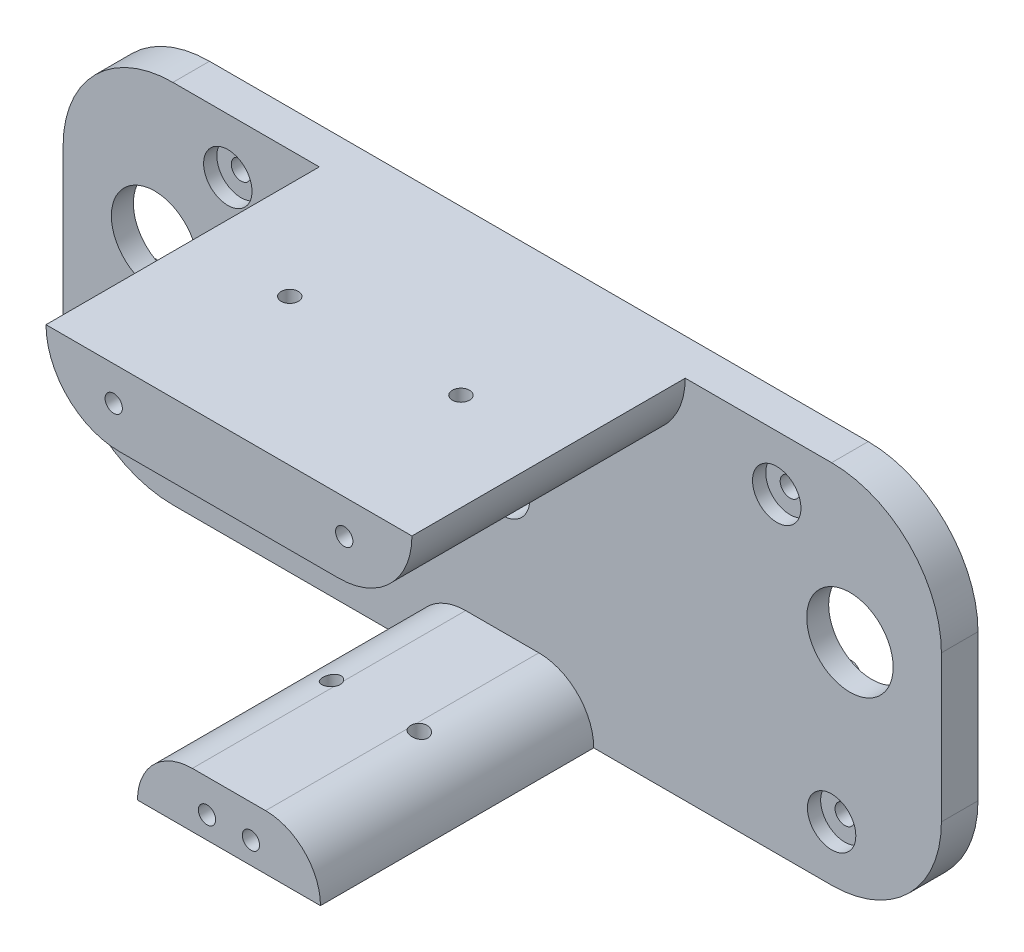
SolidWorks part; units mm, degrees
ref_plane "Front Plane" through (0, 0, 0) normal (0, 0, 1) x (1, 0, 0)
ref_plane "Top Plane" through (0, 0, 0) normal (0, 1, 0) x (1, 0, 0)
ref_plane "Right Plane" through (0, 0, 0) normal (1, 0, 0) x (0, 0, -1)
sketch "Sketch1" plane through (0, 0, 0) normal (0, 0, 1) x (1, 0, 0)
  line L0 (-57.15, 44.175) -> (57.15, 44.175)
  line L1 (76.2, 25.125) -> (76.2, -0.275)
  line L2 (57.15, -19.325) -> (-57.15, -19.325)
  line L3 (-76.2, -0.275) -> (-76.2, 25.125)
  arc A0 (-76.2, 25.125) -> (-57.15, 44.175) centre (-57.15, 25.125) cw
  arc A1 (57.15, 44.175) -> (76.2, 25.125) centre (57.15, 25.125) cw
  arc A2 (76.2, -0.275) -> (57.15, -19.325) centre (57.15, -0.275) cw
  arc A3 (-57.15, -19.325) -> (-76.2, -0.275) centre (-57.15, -0.275) cw
  point P6 (0, -19.325)
  point P7 (0, 44.175)
  dimension "D3" = 25.4
  dimension "D4" = 19.325
  dimension "D1" = 63.5
  dimension "D2" = 152.4
extrude "Boss-Extrude1" add sketch "Sketch1" along normal mid plane 6.35
sketch "Sketch2" plane through (0, 0, 3.175) normal (0, 0, -1) x (-1, 0, 0)
  line L0 (-31.75, 44.175) -> (31.75, 44.175)
  line L1 (-57.15, 44.175) -> (57.15, 44.175) construction
  line L2 (19.05, 31.475) -> (-19.05, 31.475)
  line L3 (-15.875, -19.325) -> (15.875, -19.325)
  line L5 (57.15, -19.325) -> (-57.15, -19.325) construction
  line L7 (-15.875, -19.325) -> (-15.875, -9.8)
  line L8 (-15.875, -9.8) -> (15.875, -9.8)
  line L9 (15.875, -9.8) -> (15.875, -19.325)
  arc A0 (-31.75, 44.175) -> (-19.05, 31.475) centre (-19.05, 44.175) ccw
  arc A1 (19.05, 31.475) -> (31.75, 44.175) centre (19.05, 44.175) ccw
  point P5 (0, 44.175)
  point P8 (0, 31.475)
  point P16 (0, -19.325)
  dimension "D1" = 63.5
  dimension "D2" = 38.1
  dimension "D3" = 31.75
  dimension "D4" = 9.525
extrude "Boss-Extrude2" add sketch "Sketch2" against normal blind 47.42
sketch "Sketch3" plane through (0, 0, 50.595) normal (0, 0, 1) x (1, 0, 0)
  circle A0 centre (-20, 38.225) radius 1.5
  circle A1 centre (20, 38.225) radius 1.5
  circle A2 centre (-3.81, -15.515) radius 1.5
  circle A3 centre (3.81, -15.515) radius 1.5
  dimension "D1" = 3
extrude "Cut-Extrude1" cut sketch "Sketch3" against normal blind 12.7
sketch "Sketch6" plane through (0, 44.175, 0) normal (0, 1, 0) x (1, 0, 0)
  line L0 (-31.75, -50.595) -> (31.75, -50.595) construction
  line L2 (0, -29.5735) -> (0, 29.5735) construction
  line L3 (-31.75, -50.595) -> (-31.75, -3.175) construction
  circle A0 centre (-14.85, -25.195) radius 1.5
  circle A1 centre (14.85, -25.195) radius 1.5
  dimension "D1" = 3
  dimension "D2" = 25.4
  dimension "D3" = 16.9
extrude "Cut-Extrude2" cut sketch "Sketch6" against normal blind 12.7
sketch "Sketch7" plane through (0, -19.325, 0) normal (0, -1, 0) x (1, 0, 0)
  line L0 (15.875, 50.595) -> (-15.875, 50.595) construction
  line L2 (0, -29.5735) -> (0, 29.5735) construction
  line L5 (-15.875, 50.595) -> (-15.875, 3.175) construction
  circle A0 centre (-7.62, 25.195) radius 1.5
  circle A1 centre (7.62, 25.195) radius 1.5
  dimension "D1" = 3
  dimension "D2" = 25.4
  dimension "D3" = 8.255
extrude "Cut-Extrude3" cut sketch "Sketch7" against normal blind 12.7
fillet "Fillet1" radius 9.525
hole_wizard "CBORE for #00 Binding Head Machine Screw1" [suppressed] positions "Sketch15" profile "Sketch16" counterbore size "#00" standard "ANSI Inch"
sketch "Sketch15" plane through (0, 0, 3.175) normal (0, 0, -1) x (-1, 0, 0)
  line L0 (-76.2, -0.275) -> (-76.2, 25.125) construction
  line L1 (-57.15, 44.175) -> (57.15, 44.175) construction
  line L2 (76.2, 25.125) -> (76.2, -0.275) construction
  point P0 (-60.325, 18.775)
  point P2 (60.325, 18.775)
  dimension "D1" = 15.875
  dimension "D2" = 25.4
  dimension "1" = 25.4
  dimension "D3" = 15.875
sketch "Sketch16" plane through (60.325, 18.775, -3.175) normal (1, 0, 0) x (0, 1, 0)
  line L0 (0, 0) -> (0, 53.77)
  line L1 (0, 53.77) -> (6, 53.77)
  line L3 (6, 53.77) -> (6, 4)
  line L4 (6, 4) -> (8, 4)
  line L5 (8, 4) -> (8, 0)
  line L7 (8, 0) -> (0, 0)
  line L11 (0, -6.35) -> (0, 107.95) construction
  dimension "Thru Hole Dia." = 12
  dimension "Thru Hole Depth" = 53.77
  dimension "C'Bore Dia." = 16
  dimension "C'Bore Depth" = 4
sketch "Sketch12" plane through (0, 0, 3.175) normal (0, 0, 1) x (1, 0, 0)
  line L0 (76.2, -0.275) -> (76.2, 25.125) construction
  line L1 (57.15, 44.175) -> (31.75, 44.175) construction
  line L2 (0, -29.5735) -> (0, 29.5735) construction
  circle A0 centre (60.325, 18.775) radius 7.5
  circle A1 centre (-60.325, 18.775) radius 7.5
  dimension "D1" = 15
  dimension "D2" = 15.875
  dimension "D3" = 25.4
extrude "Cut-Extrude4" cut sketch "Sketch12" against normal through all
sketch "Sketch14" plane through (0, 0, -3.175) normal (0, 0, -1) x (-1, 0, 0)
  line L0 (-64.075, 25.2702) -> (-62.2756, 33.2167) construction
  line L1 (-56.575, 25.2702) -> (-58.3744, 33.2167) construction
  line L3 (-66.0861, 23.5771) -> (-63.8239, 33.5673)
  line L4 (-54.5639, 23.5771) -> (-56.8261, 33.5673)
  line L5 (-59.0468, 26.1653) -> (-49.264, 29.2013)
  line L6 (-53.2857, 16.1868) -> (-45.765, 23.141)
  line L7 (-53.2857, 21.3632) -> (-45.765, 14.409)
  line L8 (-59.0468, 11.3847) -> (-49.264, 8.3487)
  line L9 (-54.5639, 13.9729) -> (-56.8261, 3.9827)
  line L10 (-66.0861, 13.9729) -> (-63.8239, 3.9827)
  line L11 (-61.6032, 11.3847) -> (-71.386, 8.3487)
  line L12 (-67.3643, 21.3632) -> (-74.885, 14.409)
  line L13 (-67.3643, 16.1868) -> (-74.885, 23.141)
  line L14 (-61.6032, 26.1653) -> (-71.386, 29.2013)
  circle A0 centre (-60.325, 18.775) radius 7.5 construction
  arc A1 (-62.2756, 33.2167) -> (-58.3744, 33.2167) centre (-60.325, 32.775) cw construction
  arc A2 (-63.8239, 33.5673) -> (-56.8261, 33.5673) centre (-60.325, 32.775) cw
  arc A3 (-49.264, 29.2013) -> (-45.765, 23.141) centre (-48.2006, 25.775) cw
  arc A4 (-45.765, 14.409) -> (-49.264, 8.3487) centre (-48.2006, 11.775) cw
  arc A5 (-56.8261, 3.9827) -> (-63.8239, 3.9827) centre (-60.325, 4.775) cw
  arc A6 (-71.386, 8.3487) -> (-74.885, 14.409) centre (-72.4494, 11.775) cw
  arc A7 (-74.885, 23.141) -> (-71.386, 29.2013) centre (-72.4494, 25.775) cw
  point P13 (-60.325, 36.3625)
  point P14 (-60.325, 34.775)
  point P43 (-60.325, 18.775)
  circle M3 centre (-60.325, 18.775) radius 7.5
  dimension "D2" = 2
  dimension "D1" = 8.1477
  dimension "D3" = 25.2702
  dimension "D4" = 1.5875
  dimension "D5" = 1.5875
  dimension "D8" = 1.5875
extrude "Cut-Extrude5" cut sketch "Sketch14" against normal blind 2.54 contours A7 L13 L12 L3 L14 M3 | L14 L3 M3 | A2 L3 L14 L5 L4 M3 | L5 L4 M3 | A3 L5 L4 L7 L6 M3 | L7 L6 M3 | A4 L7 L6 L9 L8 M3 | L9 L8 M3 | A5 L9 L8 L11 L10 M3 | L11 L10 M3 | A6 L11 L10 L13 L12 M3 | L13 L12 M3
fillet "Fillet3" radius 1.5875
mirror "Mirror2" about plane through (0, 0, 0) normal (1, 0, 0) of "Fillet3", "Cut-Extrude5"
hole_wizard "CBORE for M3 Hex Head Machine Screw1" positions "Sketch17" profile "Sketch18" counterbore size "M3" standard "ANSI Metric"
sketch "Sketch17" plane through (0, 0, 3.175) normal (0, 0, 1) x (1, 0, 0)
  line L0 (-76.2, 25.125) -> (-76.2, -0.275) construction
  line L1 (-31.75, 44.175) -> (-57.15, 44.175) construction
  line L2 (-57.15, -19.325) -> (-15.875, -19.325) construction
  line L3 (76.2, -0.275) -> (76.2, 25.125) construction
  point P0 (-47.625, 34.65)
  point P2 (-57.15, -9.8)
  point P4 (57.15, -9.8)
  point P6 (47.625, 34.65)
  dimension "D1" = 28.575
  dimension "D2" = 9.525
  dimension "D3" = 19.05
  dimension "D4" = 9.525
  dimension "D5" = 28.575
  dimension "D6" = 19.05
sketch "Sketch18" plane through (-47.625, 34.65, 3.175) normal (1, 0, 0) x (0, -1, 0)
  line L0 (0, 0) -> (0, 6.35)
  line L1 (0, 6.35) -> (1.7, 6.35)
  line L3 (1.7, 6.35) -> (1.7, 2.3)
  line L4 (1.7, 2.3) -> (4.2, 2.3)
  line L5 (4.2, 2.3) -> (4.2, 0)
  line L7 (4.2, 0) -> (0, 0)
  line L11 (0, -6.35) -> (0, 107.95) construction
  dimension "Thru Hole Dia." = 3.4
  dimension "Thru Hole Depth" = 6.35
  dimension "C'Bore Dia." = 8.4
  dimension "C'Bore Depth" = 2.3
sketch "Sketch19" plane through (0, 0, 3.175) normal (0, 0, 1) x (1, 0, 0)
  line L0 (-57.15, -19.325) -> (-15.875, -19.325) construction
  circle A0 centre (0, 12.425) radius 4.7625
  dimension "D1" = 9.525
  dimension "D2" = 31.75
extrude "Cut-Extrude6" cut sketch "Sketch19" against normal through all
